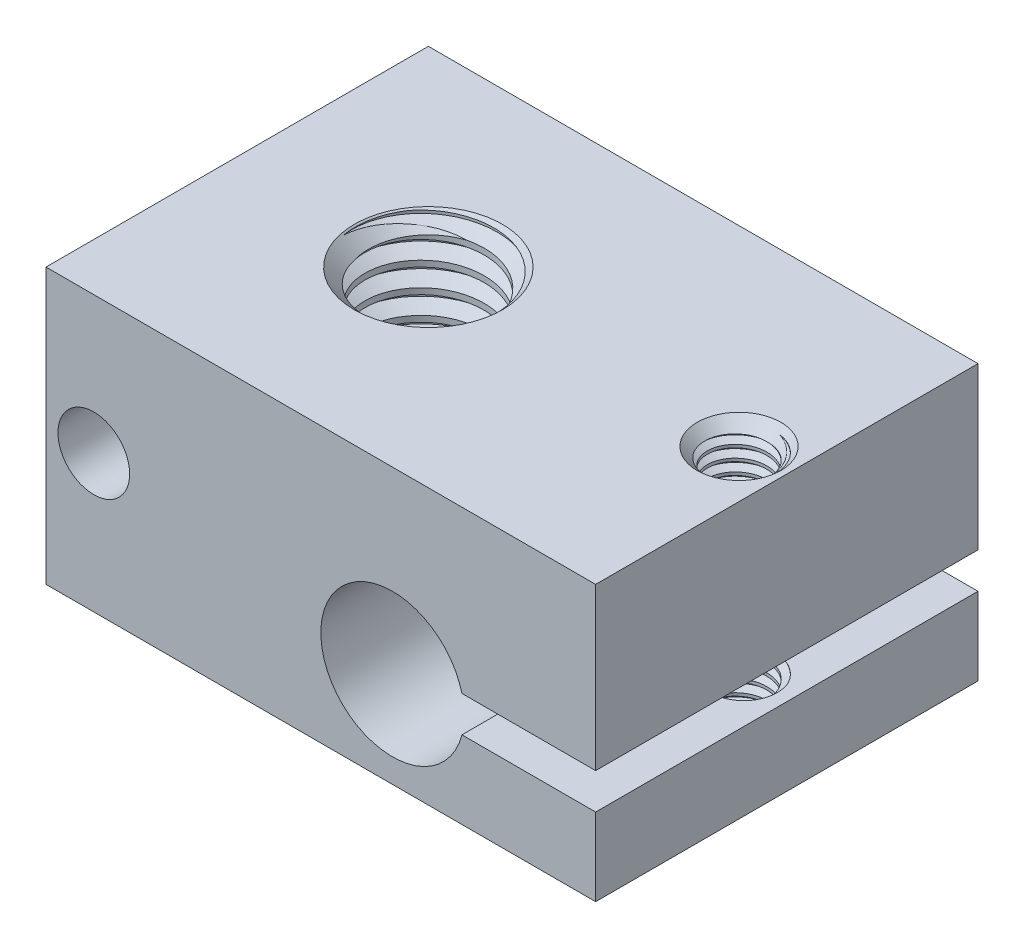
SolidWorks part; units mm, degrees
note: The reader was unsure of these and kept them because the rebuilt part matched: shared geometry of "Sketch2<3>".
material "Brass"
ref_plane "Front Plane" through (0, 0, 0) normal (0, 0, 1) x (1, 0, 0)
ref_plane "Top Plane" through (0, 0, 0) normal (0, 1, 0) x (1, 0, 0)
ref_plane "Right Plane" through (0, 0, 0) normal (1, 0, 0) x (0, 0, -1)
sketch "Sketch1" plane through (0, 0, 0) normal (0, 1, 0) x (1, 0, 0)
  line L0 (-11.5, -8) -> (11.5, 8) construction
  line L1 (-11.5, 8) -> (11.5, 8)
  line L2 (-11.5, 8) -> (-11.5, -8)
  line L3 (-11.5, -8) -> (11.5, -8)
  line L4 (11.5, 8) -> (11.5, -8)
  circle A0 centre (-3.5, 0) radius 2.5
  point P6 (0, 0)
  point P7 (0, 0)
  dimension "D3" = 5
  dimension "D1" = 16
  dimension "D2" = 23
  dimension "D4" = 8
extrude "Boss-Extrude1" add sketch "Sketch1" along normal blind 11.5
sketch "Sketch2" plane through (0, 0, 0) normal (0, -1, 0) x (1, 0, 0)
  line L0 (-9.5, 0) -> (-11.5, 0) construction
  line L1 (-11.5, -8) -> (-11.5, 8) construction
  line L2 (9.5, 0) -> (11.5, 0) construction
  line L3 (11.5, 8) -> (11.5, -8) construction
  circle A0 centre (-9.5, 0) radius 1.25
  circle A1 centre (9.5, 0) radius 1.25
  dimension "D1" = 2.5
  dimension "D2" = 2
sketch "Sketch3" plane through (0, 0, 8) normal (0, 0, 1) x (1, 0, 0)
  line L0 (3, 4) -> (-11.5, 4) construction
  line L1 (-11.5, 11.5) -> (-11.5, 0) construction
  line L2 (3, 4) -> (3, 0) construction
  line L3 (-11.5, 0) -> (11.5, 0) construction
  line L4 (-9.5, 5.75) -> (-11.5, 5.75) construction
  line L5 (-9.5, 5.75) -> (-9.5, 0) construction
  line L6 (3, 4) -> (11.5, 4) construction
  line L7 (11.5, 11.5) -> (11.5, 0) construction
  line L8 (5.9047, 3.25) -> (11.5, 3.25)
  line L9 (5.9047, 4.75) -> (11.5, 4.75)
  line L10 (11.5, 4.75) -> (11.5, 3.25)
  line L11 (3, 4.75) -> (11.5, 4.75) construction
  line L12 (3, 3.25) -> (11.5, 3.25) construction
  circle A0 centre (-9.5, 5.75) radius 1.5
  arc A1 (5.9047, 4.75) -> (5.9047, 3.25) centre (3, 4) ccw
  dimension "D1" = 3
  dimension "D2" = 6
  dimension "D3" = 14.5
  dimension "D4" = 4
  dimension "D5" = 5.75
  dimension "D6" = 2
  dimension "D7" = 0.75
  dimension "D8" = 0.75
extrude "Cut-Extrude1" cut sketch "Sketch3" against normal through all
extrude "Cut-Extrude2" cut sketch "Sketch2" against normal through all contours A1
extrude "Cut-Extrude3" cut sketch "Sketch2<3>" against normal blind 5.75 contours A0
sketch "Sketch2<3>" plane through (0, 0, 0) normal (0, -1, 0) x (1, 0, 0) same geometry as "Sketch2"
chamfer "Chamfer1" distance 0.6 angle 45 2 edges at (-3.5, 0, 2.5) (-3.5, 11.5, 2.5)
chamfer "Chamfer2" distance 0.5 angle 45 3 edges at (9.5, 11.5, -1.25) (9.5, 0, -1.25) (-9.5, 0, -1.25)
thread "Thread1" pitch 1 start angle 0, offset 5, length 20, pitch 1, diameter 5
ref_plane "Plane1" through (-1, -4.4, 0) normal (0, 0, 1) x (1, 0, 0)
sketch "Thread Profile1" plane through (-1, -4.4, 0) normal (0, 0, 1) x (1, 0, 0)
  line L0 (0, 0) -> (0, 1) construction
  line L1 (0, 0) -> (0.5413, 0.3125)
  line L2 (0.5413, 0.3125) -> (0.5413, 0.4375)
  line L3 (0.5413, 0.4375) -> (0, 0.75)
  line L4 (0.5413, 0.375) -> (0, 0.375) construction
  line L11 (0, 0) -> (0, 0.75)
  point P2 (0, 0)
  dimension "Pitch" = 1
  dimension "Profile_Angle" = 60
  dimension "Profile_Land" = 0.125
  dimension "Profile_Height" = 0.5413
thread "Thread2" pitch 0.5 profile "Thread Profile2" start angle 0, offset 1, length 5, pitch 0.5, diameter 2.5
ref_plane "Plane2" through (-8.25, -0.5, 0) normal (0, 0, 1) x (1, 0, 0)
sketch "Thread Profile2" plane through (-8.25, -0.5, 0) normal (0, 0, 1) x (1, 0, 0)
  line L0 (0, 0) -> (0, 0.5) construction
  line L1 (0, 0) -> (0.2706, 0.1562)
  line L2 (0.2706, 0.1562) -> (0.2706, 0.2187)
  line L3 (0.2706, 0.2187) -> (0, 0.375)
  line L4 (0.2706, 0.1875) -> (0, 0.1875) construction
  line L11 (0, 0) -> (0, 0.375)
  point P2 (0, 0)
  dimension "Pitch" = 0.5
  dimension "Profile_Angle" = 60
  dimension "Profile_Land" = 0.0625
  dimension "Profile_Height" = 0.2706
thread "Thread3" pitch 0.5 profile "Thread Profile3" start angle 0, offset 1, length 15, pitch 0.5, diameter 2.5
ref_plane "Plane3" through (10.75, -0.5, 0) normal (0, 0, 1) x (1, 0, 0)
sketch "Thread Profile3" plane through (10.75, -0.5, 0) normal (0, 0, 1) x (1, 0, 0)
  line L0 (0, 0) -> (0, 0.5) construction
  line L1 (0, 0) -> (0.2706, 0.1562)
  line L2 (0.2706, 0.1562) -> (0.2706, 0.2187)
  line L3 (0.2706, 0.2187) -> (0, 0.375)
  line L4 (0.2706, 0.1875) -> (0, 0.1875) construction
  line L11 (0, 0) -> (0, 0.375)
  point P2 (0, 0)
  dimension "Pitch" = 0.5
  dimension "Profile_Angle" = 60
  dimension "Profile_Land" = 0.0625
  dimension "Profile_Height" = 0.2706
